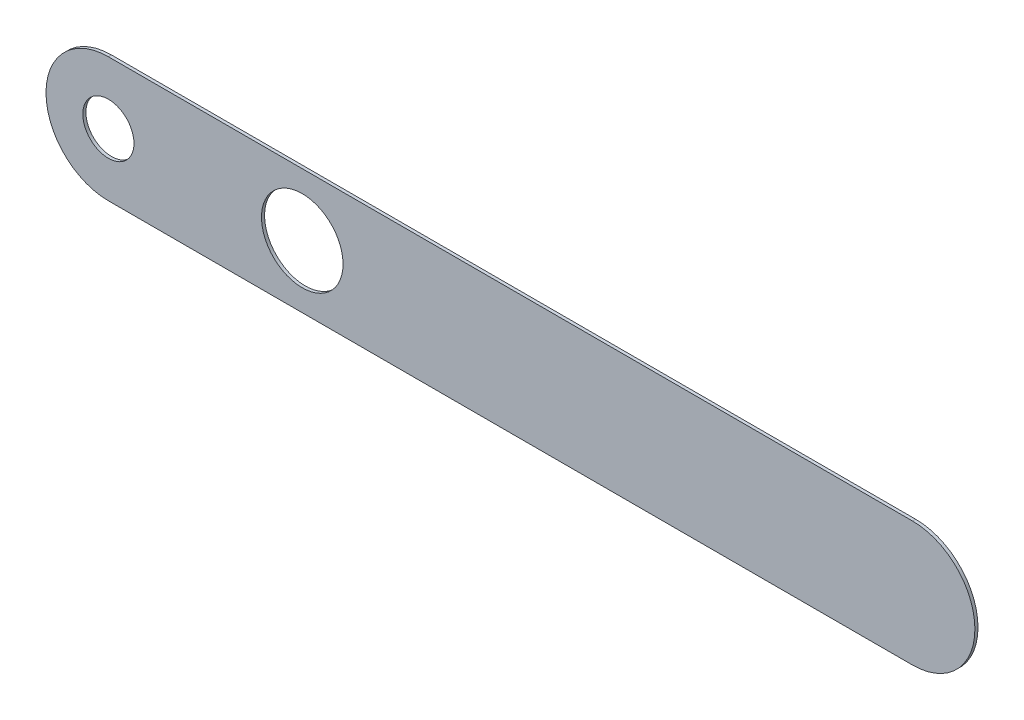
SolidWorks part; units mm, degrees
ref_plane "Front Plane" through (0, 0, 0) normal (0, 0, 1) x (1, 0, 0)
ref_plane "Top Plane" through (0, 0, 0) normal (0, 1, 0) x (1, 0, 0)
ref_plane "Right Plane" through (0, 0, 0) normal (1, 0, 0) x (0, 0, -1)
sketch "Sketch1" plane through (0, 0, 0) normal (0, 0, 1) x (1, 0, 0)
  line L0 (-120.9134, 0) -> (69.7147, 0) construction
  line L1 (-120.9134, 14.788) -> (69.7147, 14.788)
  line L2 (-120.9134, -14.788) -> (69.7147, -14.788)
  arc A0 (-120.9134, 14.788) -> (-120.9134, -14.788) centre (-120.9134, 0) ccw
  arc A1 (69.7147, -14.788) -> (69.7147, 14.788) centre (69.7147, 0) ccw
  circle A2 centre (-74.9531, 0) radius 9.6655
  circle A3 centre (-120.9134, 0) radius 6.0637
  point P3 (-25.5993, 0)
base flange "Base-Flange1" sketch "Sketch1" thickness 0.7366 reverse thickness direction no parameters "D1"=0.7366
sketch "Bend-Lines1" plane through (0, 0, 0) normal (0, 1, 0) x (1, 0, 0)
sketch "Bounding-Box1" plane through (0, 0, 0) normal (0, 1, 0) x (1, 0, 0)
sheet metal parameters "Sheet-Metal1" thickness 0.7366 parameters "D1"=0.7366
flat pattern "Flat-Pattern1" [suppressed]
sketch "Bend-Lines2" plane through (0, 0, 0) normal (0, 1, 0) x (1, 0, 0)
sketch "Bounding-Box2" [suppressed] plane through (0, 0, 0) normal (0, 1, 0) x (1, 0, 0)
